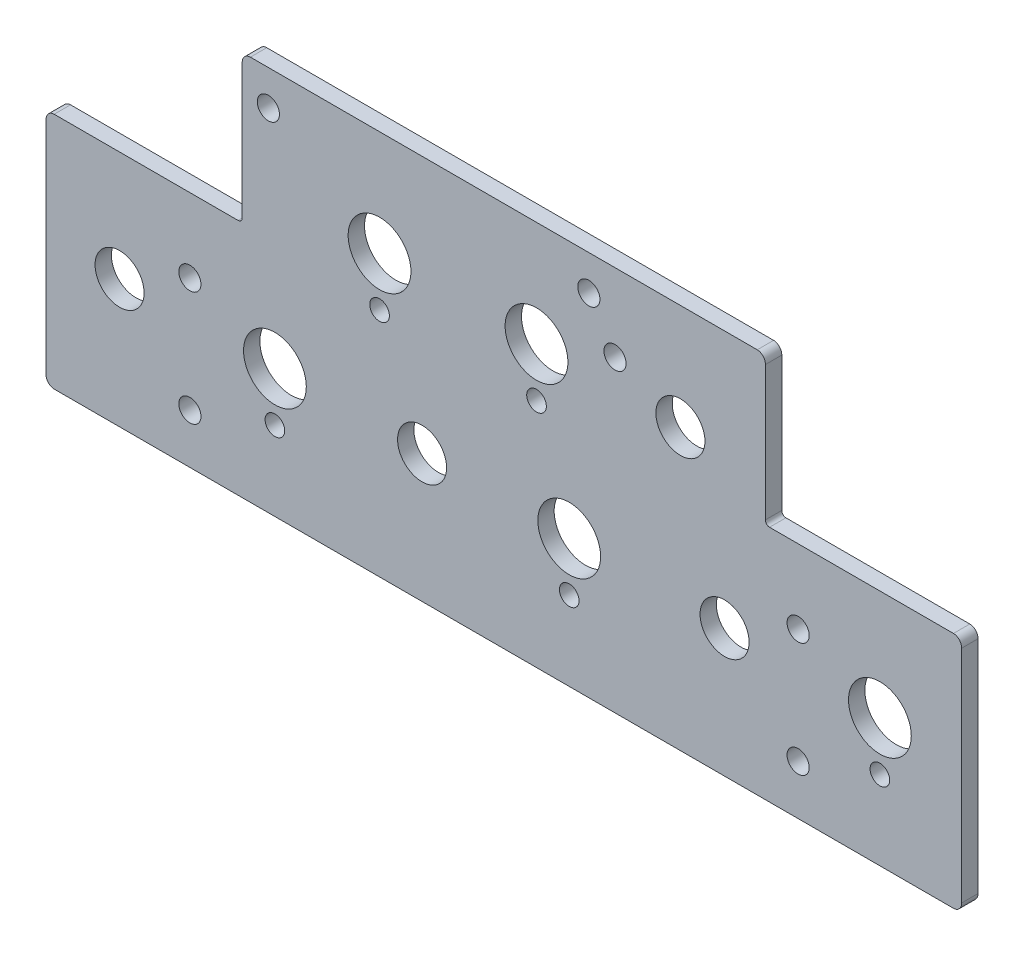
SolidWorks part; units mm, degrees
material "Acrylic (Medium-high impact)"
ref_plane "Front Plane" through (0, 0, 0) normal (0, 0, 1) x (1, 0, 0)
ref_plane "Top Plane" through (0, 0, 0) normal (0, 1, 0) x (1, 0, 0)
ref_plane "Right Plane" through (0, 0, 0) normal (1, 0, 0) x (0, 0, -1)
sketch "Sketch1" plane through (0, 0, 0) normal (0, 0, 1) x (1, 0, 0)
  line L8 (-51.5937, 5.4323) -> (-87.3125, 5.4323)
  line L9 (-88.9, 3.7429) -> (-88.9, -39.0998)
  line L10 (-87.3125, -40.7892) -> (87.3125, -40.7892)
  line L11 (88.9, -39.0998) -> (88.9, 3.7429)
  line L12 (87.3125, 5.4323) -> (51.5938, 5.4323)
  line L13 (50.8, 6.277) -> (50.8, 32.3948)
  line L14 (49.2125, 34.0842) -> (-49.2125, 34.0842)
  line L15 (-50.8, 32.3948) -> (-50.8, 6.277)
  line L16 (-51.5937, 5.4323) -> (-87.3125, 5.4323)
  line L17 (-88.9, 3.7429) -> (-88.9, -39.0998)
  line L18 (-87.3125, -40.7892) -> (87.3125, -40.7892)
  line L19 (88.9, -39.0998) -> (88.9, 3.7429)
  line L20 (87.3125, 5.4323) -> (51.5938, 5.4323)
  line L21 (50.8, 6.277) -> (50.8, 32.3948)
  line L22 (49.2125, 34.0842) -> (-49.2125, 34.0842)
  line L23 (-50.8, 32.3948) -> (-50.8, 6.277)
  ellipse E8 centre (87.3125, 3.7429) end of major axis (87.3125, 2.0535) minor radius 1.5875 (88.9, 3.7429) -> (87.3125, 5.4323) ccw
  ellipse E9 centre (87.3125, 3.7429) end of major axis (87.3125, 2.0535) minor radius 1.5875 (88.9, 3.7429) -> (87.3125, 5.4323) ccw
  ellipse E10 centre (49.2125, 32.3948) end of major axis (49.2125, 34.0842) minor radius 1.5875 (50.8, 32.3948) -> (49.2125, 34.0842) ccw
  ellipse E11 centre (49.2125, 32.3948) end of major axis (49.2125, 34.0842) minor radius 1.5875 (50.8, 32.3948) -> (49.2125, 34.0842) ccw
  ellipse E12 centre (51.5938, 6.277) end of major axis (51.5938, 5.4323) minor radius 0.7938 (50.8, 6.277) -> (51.5938, 5.4323) ccw
  ellipse E13 centre (51.5938, 6.277) end of major axis (51.5938, 5.4323) minor radius 0.7938 (50.8, 6.277) -> (51.5938, 5.4323) ccw
  ellipse E14 centre (-51.5937, 6.277) end of major axis (-51.5937, 5.4323) minor radius 0.7938 (-51.5937, 5.4323) -> (-50.8, 6.277) ccw
  ellipse E15 centre (-51.5937, 6.277) end of major axis (-51.5937, 5.4323) minor radius 0.7938 (-51.5937, 5.4323) -> (-50.8, 6.277) ccw
  ellipse E28 centre (-49.2125, 32.3948) end of major axis (-49.2125, 34.0842) minor radius 1.5875 (-49.2125, 34.0842) -> (-50.8, 32.3948) ccw
  ellipse E29 centre (-49.2125, 32.3948) end of major axis (-49.2125, 34.0842) minor radius 1.5875 (-49.2125, 34.0842) -> (-50.8, 32.3948) ccw
  ellipse E30 centre (-87.3125, 3.7429) end of major axis (-87.3125, 2.0535) minor radius 1.5875 (-87.3125, 5.4323) -> (-88.9, 3.7429) ccw
  ellipse E31 centre (-87.3125, 3.7429) end of major axis (-87.3125, 2.0535) minor radius 1.5875 (-87.3125, 5.4323) -> (-88.9, 3.7429) ccw
  ellipse E32 centre (-87.3125, -39.0998) end of major axis (-87.3125, -37.4104) minor radius 1.5875 (-88.9, -39.0998) -> (-87.3125, -40.7892) ccw
  ellipse E33 centre (-87.3125, -39.0998) end of major axis (-87.3125, -37.4104) minor radius 1.5875 (-88.9, -39.0998) -> (-87.3125, -40.7892) ccw
  ellipse E34 centre (87.3125, -39.0998) end of major axis (87.3125, -37.4104) minor radius 1.5875 (87.3125, -40.7892) -> (88.9, -39.0998) ccw
  ellipse E35 centre (87.3125, -39.0998) end of major axis (87.3125, -37.4104) minor radius 1.5875 (87.3125, -40.7892) -> (88.9, -39.0998) ccw
  dimension "D1" = 0
extrude "Boss-Extrude1" add sketch "Sketch1" along normal blind 3.175
sketch "Sketch2" plane through (0, 0, 3.175) normal (0, 0, 1) x (1, 0, 0)
  arc A4 (-72.0725, -25.0899) -> (-77.1525, -25.0899) centre (-74.6125, -15.9098) ccw construction
  arc A5 (-14.2875, -23.6221) -> (-17.4625, -23.6221) centre (-15.875, -15.9098) ccw construction
  arc A6 (45.4025, -25.0899) -> (40.3225, -25.0899) centre (42.8625, -15.9098) ccw construction
  arc A7 (35.8775, 5.9054) -> (32.7025, 5.9054) centre (34.29, 13.6177) ccw construction
  circle A8 centre (42.8625, -15.9098) radius 4.7625
  circle A9 centre (-15.875, -15.9098) radius 4.7625
  circle A10 centre (-74.6125, -15.9098) radius 4.7625
  circle A11 centre (34.29, 13.6177) radius 4.7625
  dimension "D1" = 9.525
extrude "Cut-Extrude1" cut sketch "Sketch2" against normal through all
sketch "Sketch4" plane through (0, 0, 3.175) normal (0, 0, 1) x (1, 0, 0)
  circle A0 centre (73.025, -15.9098) radius 6.096
  circle A1 centre (12.7, -15.9098) radius 6.096
  circle A2 centre (-44.45, -15.9098) radius 6.096
  circle A3 centre (-24.13, 13.6177) radius 6.096
  circle A4 centre (6.35, 13.6177) radius 6.096
  circle A5 centre (73.025, -25.4348) radius 1.905
  circle A6 centre (12.7, -25.4348) radius 1.905
  circle A7 centre (-44.45, -25.4348) radius 1.905
  circle A8 centre (6.35, 4.0927) radius 1.905
  circle A9 centre (-24.13, 4.0927) radius 1.905
  dimension "D1" = 12.192
  dimension "D2" = 3.81
  dimension "D3" = 9.525
  dimension "D4" = 9.525
extrude "Cut-Extrude2" cut sketch "Sketch4" against normal through all
hole_wizard "#6 Clearance Hole1" positions "Sketch6" profile "Sketch5" hole size "#6" standard "ANSI Inch" end condition through all
sketch "Sketch6" plane through (0, 0, 3.175) normal (0, 0, 1) x (1, 0, 0)
  point P0 (-45.72, 27.2702)
  point P3 (16.51, 27.2702)
  point P6 (21.59, 19.0152)
  point P9 (57.15, -8.9248)
  point P12 (57.15, -31.1498)
  point P15 (-60.96, -31.1498)
  point P18 (-60.96, -8.9248)
sketch "Sketch5" plane through (-45.72, 27.2702, 3.175) normal (1, 0, 0) x (0, -1, 0)
  line L0 (0, 0) -> (0, 3.175)
  line L1 (0, 3.175) -> (2.1526, 3.175)
  line L2 (2.1526, 3.175) -> (2.1526, 0)
  line L5 (2.1526, 0) -> (0, 0)
  line L11 (0, -6.35) -> (0, 107.95) construction
  dimension "Thru Hole Dia." = 4.3053
  dimension "Thru Hole Depth" = 3.175
fillet "Fillet1" [suppressed] radius 1.5875
equation "\"D4@Sketch4\"=\"D3@Sketch4\""
